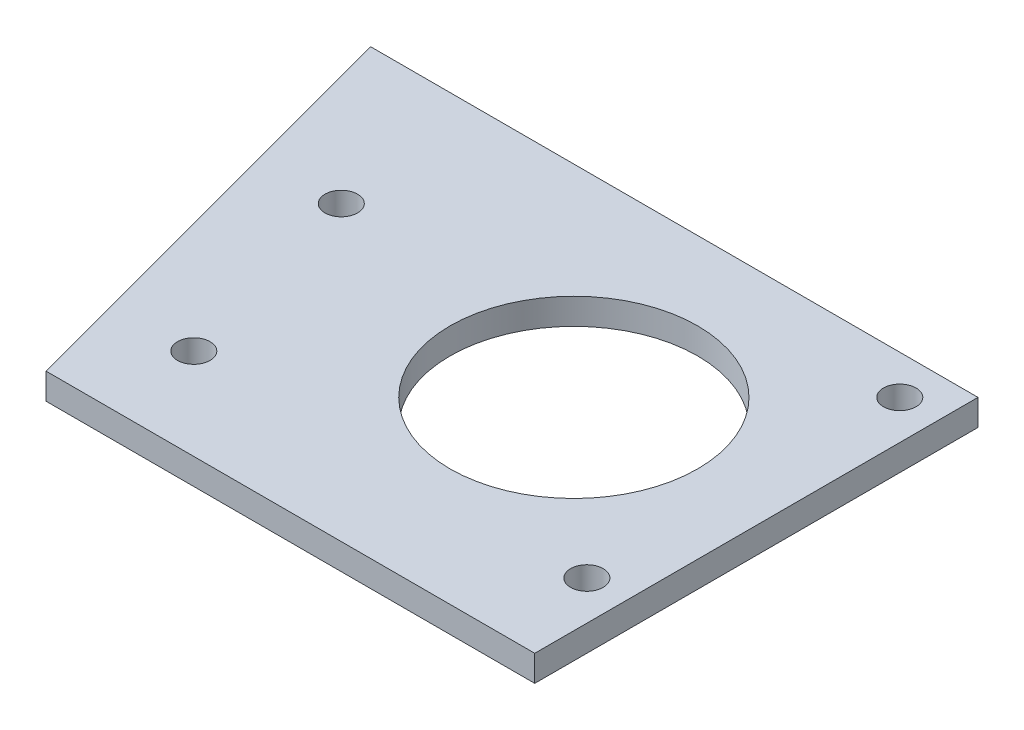
SolidWorks part; units mm, degrees
material "1.0553 (S355J0)"
ref_plane "Płaszczyzna przednia" through (0, 0, 0) normal (0, 0, 1) x (1, 0, 0)
ref_plane "Płaszczyzna górna" through (0, 0, 0) normal (0, 1, 0) x (1, 0, 0)
ref_plane "Płaszczyzna prawa" through (0, 0, 0) normal (1, 0, 0) x (0, 0, -1)
sketch "Szkic1" plane through (0, 0, 0) normal (0, 1, 0) x (1, 0, 0)
  line L1 (-463.5553, -566.5676) -> (463.5553, -566.5676)
  line L2 (-463.5553, -566.5676) -> (-463.5553, 566.5676)
  line L3 (-463.5553, 566.5676) -> (463.5553, 566.5676)
  line L4 (463.5553, -566.5676) -> (463.5553, 566.5676)
  point P4 (0, 566.5676)
  point P6 (-463.5553, 0)
sketch "Szkic2" [suppressed] plane through (0, 0, 0) normal (0, 1, 0) x (1, 0, 0)
  line L1 (-65, 65) -> (65, 65)
  line L2 (-65, 65) -> (-65, -65)
  line L3 (-65, -65) -> (65, -65)
  line L4 (65, 65) -> (65, -65)
  circle A0 centre (0, 0) radius 37.5
  circle A1 centre (0, -53) radius 5.25
  point P12 (65, 0)
  point P15 (0, 65)
  dimension "D2" = 10.5
  dimension "D3" = 75
  dimension "D1" = 53
  dimension "D4" = 130
  dimension "D5" = 130
extrude "Dodanie-wyciągnięcie1" [suppressed] add sketch "Szkic2" along normal blind 10
pattern_circular "Szyk kołowy1" [suppressed] count 4 every 90 of bodies 102
chamfer "Sfazowanie1" [suppressed] distance 20 angle 45
sketch "Szkic3" plane through (0, 0, 0) normal (0, 1, 0) x (1, 0, 0)
  line L3 (-77.5, 77.5) -> (77.5, 77.5)
  line L4 (77.5, -77.5) -> (77.5, 77.5)
  line L6 (-109.9486, -92.5) -> (-155.5, 77.5)
  line L7 (-155.5, 77.5) -> (-77.5, 77.5)
  line L8 (-109.9486, -92.5) -> (-270.1261, -92.5) construction
  line L9 (77.5, -77.5) -> (77.5, -92.5)
  line L10 (77.5, -92.5) -> (-109.9486, -92.5)
  line L11 (-108.9741, 19.7741) -> (-88.2686, -57.5) construction
  line L12 (-88.2686, -57.5) -> (-117.2463, -65.2646) construction
  circle A0 centre (0, 0) radius 47.5
  circle A1 centre (62.5, 62.5) radius 6.25
  circle A2 centre (62.5, -57.5) radius 6.25
  circle A3 centre (-88.2686, -57.5) radius 6.25
  circle A4 centre (-108.9741, 19.7741) radius 6.25
  point P4 (0, 77.5)
  point P6 (77.5, 0)
  dimension "D1" = 95
  dimension "D7" = 12.5
  dimension "D10" = 120
  dimension "D2" = 155
  dimension "D3" = 155
  dimension "D4" = 15
  dimension "D5" = 78
  dimension "D6" = 75
  dimension "D8" = 15
  dimension "D9" = 15
  dimension "D11" = 30
  dimension "D12" = 80
extrude "Dodanie-wyciągnięcie2" add sketch "Szkic3" along normal blind 10
sketch "Szkic4" [suppressed] plane through (0, 10, 0) normal (0, 1, 0) x (1, 0, 0)
  line L0 (-55, 55) -> (55, -55) construction
  line L1 (-45, 65) -> (-65, 45) construction
  line L2 (45, -65) -> (65, -45) construction
  line L3 (55, 55) -> (-55, -55) construction
  line L4 (65, 45) -> (45, 65) construction
  line L5 (-65, -45) -> (-45, -65) construction
